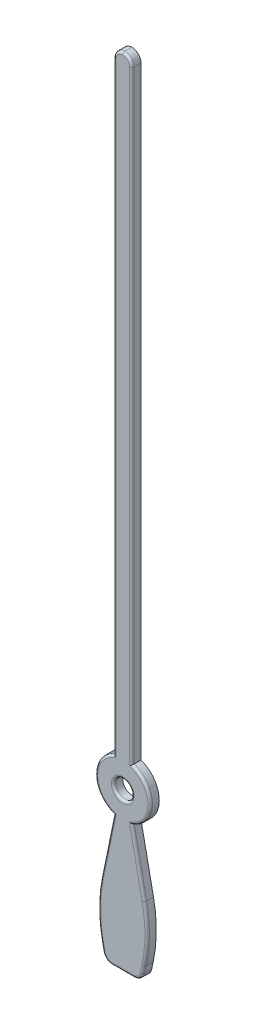
SolidWorks part; units mm, degrees
ref_plane "Front" through (0, 0, 0) normal (0, 0, 1) x (1, 0, 0)
ref_plane "Top" through (0, 0, 0) normal (0, 1, 0) x (1, 0, 0)
ref_plane "Right" through (0, 0, 0) normal (1, 0, 0) x (0, 0, -1)
sketch "Эскиз1" plane through (0, 0, 0) normal (0, 0, 1) x (1, 0, 0)
  circle A0 centre (0, 0) radius 0.6
  circle A1 centre (0, 0) radius 0.2
  dimension "D1" = 0.4
  dimension "D2" = 1.2
extrude "Бобышка-Вытянуть1" add sketch "Эскиз1" along normal blind 0.2
sketch "Эскиз3" plane through (0, 0, 0.2) normal (0, 0, 1) x (1, 0, 0)
  line L0 (0, 0) -> (0, 14) construction
  line L1 (-0.2, 0.5657) -> (-0.2, 14)
  line L2 (-0.2, 14) -> (0.2, 14)
  line L3 (0.2, 0.5657) -> (0.2, 14)
  line L4 (0, -0.6) -> (0, -5.8637) construction
  line L5 (-0.2, -0.5657) -> (-0.4736, -1.8986)
  line L6 (-0.4686, -3.1291) -> (-0.4, -3.4498)
  line L7 (-0.4, -3.4498) -> (0.4, -3.4498)
  line L8 (0.4686, -3.1291) -> (0.4, -3.4498)
  line L9 (0.2, -0.5657) -> (0.4736, -1.8986)
  circle A0 centre (0, 0) radius 0.6 construction
  arc A1 (-0.2, -0.5657) -> (0.2, -0.5657) centre (0, 0) ccw
  arc A2 (0.2, 0.5657) -> (-0.2, 0.5657) centre (0, 0) ccw
  arc A3 (0.4686, -3.1291) -> (0.4736, -1.8986) centre (-2.4651, -2.5019) ccw
  arc A4 (-0.4736, -1.8986) -> (-0.4686, -3.1291) centre (2.4651, -2.5019) ccw
  point P16 (0, -3.4498)
  point P20 (0.6, -2.5144)
  point P23 (-0.6, -2.5144)
  dimension "D3" = 3
  dimension "D1" = 14
  dimension "D2" = 0.2
extrude "Бобышка-Вытянуть2" add sketch "Эскиз3" against normal blind 0.2
fillet "Скругление1" radius 0.2 4 edges at (-0.4, -3.4498, 0.1) (0.4, -3.4498, 0.1) (-0.2, 14, 0.1) (0.2, 14, 0.1)
fillet "Скругление2" radius 0.05 16 edges at (-0.2, 7.1828, 0.2) (-0.1414, 13.9414, 0.2) (0.1414, 13.9414, 0.2) (-0.3368, -1.2322, 0.2) (-0.5349, -2.5141, 0.2) (-0.4512, -3.2104, 0.2) (-0.364, -3.4053, 0.2) (0, -3.4498, 0.2) (0.364, -3.4053, 0.2) (0.4512, -3.2104, 0.2) (0.3368, -1.2322, 0.2) (-0.6, 0, 0.2) (0.2, 7.1828, 0.2) (0.6, 0, 0.2) (0.5349, -2.5141, 0.2) (0.2, 0, 0.2)
